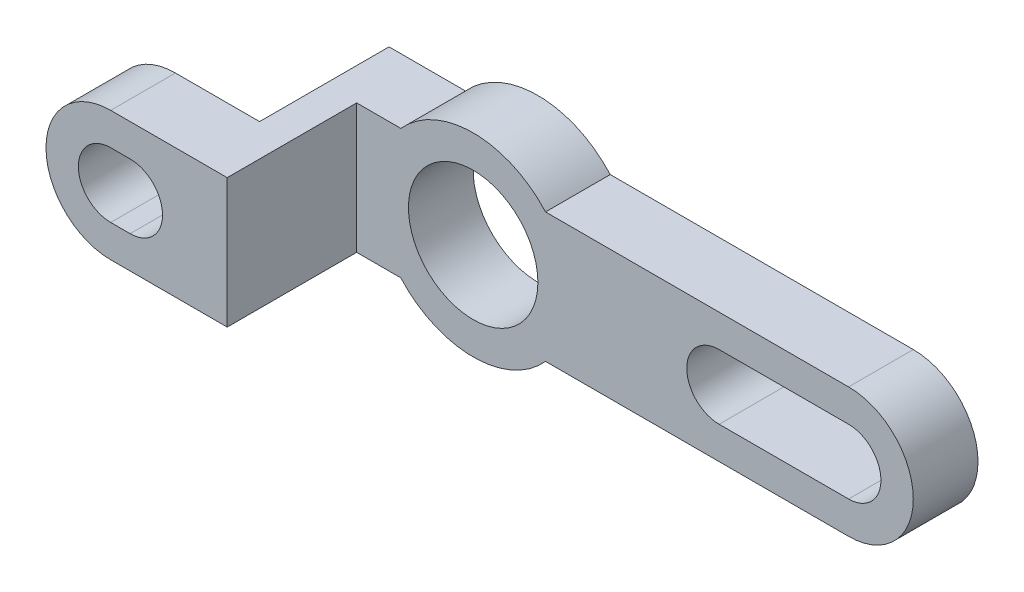
SolidWorks part; units mm, degrees
ref_plane "Front Plane" through (0, 0, 0) normal (0, 0, 1) x (1, 0, 0)
ref_plane "Top Plane" through (0, 0, 0) normal (0, 1, 0) x (1, 0, 0)
ref_plane "Right Plane" through (0, 0, 0) normal (1, 0, 0) x (0, 0, -1)
sketch "Sketch1" plane through (0, 0, 0) normal (0, 0, 1) x (1, 0, 0)
  line L0 (7.0995, 6.35) -> (31.75, 6.35)
  line L1 (-31.75, 6.35) -> (-7.0995, 6.35) construction
  line L2 (-31.75, 6.35) -> (-31.75, -6.35) construction
  line L3 (-31.75, -6.35) -> (-7.0995, -6.35) construction
  line L4 (31.75, 6.35) -> (31.75, -6.35) construction
  line L5 (-31.75, 6.35) -> (31.75, -6.35) construction
  line L6 (-31.75, -6.35) -> (31.75, 6.35) construction
  line L10 (7.0995, -6.35) -> (31.75, -6.35)
  line L14 (-17.78, 6.35) -> (-17.78, -6.35)
  line L15 (-17.78, 6.35) -> (-7.0995, 6.35)
  line L16 (-17.78, -6.35) -> (-7.0995, -6.35)
  line L17 (36.83, 6.35) -> (36.83, -6.35)
  line L18 (31.75, 6.35) -> (36.83, 6.35)
  line L19 (36.83, -6.35) -> (31.75, -6.35)
  arc A1 (-7.0995, -6.35) -> (7.0995, -6.35) centre (0, 0) ccw
  arc A5 (7.0995, 6.35) -> (-7.0995, 6.35) centre (0, 0) ccw
  circle A6 centre (0, 0) radius 6.35
  dimension "D3" = 19.05
  dimension "D4" = 12.7
  dimension "D1" = 63.5
  dimension "D2" = 12.7
  dimension "D5" = 13.97
  dimension "D6" = 36.83
extrude "Boss-Extrude1" add sketch "Sketch1" along normal mid plane 6.35
sketch "Sketch2" plane through (0, 0, -3.175) normal (0, 0, -1) x (-1, 0, 0)
  line L1 (-36.83, -6.35) -> (-36.83, 6.35) construction
  circle A0 centre (-36.83, 0) radius 6.35
  circle A1 centre (-36.83, 0) radius 3.175
  point P5 (-36.83, 0)
  dimension "D1" = 6.35
  dimension "D2" = 3.175
extrude "Boss-Extrude2" add sketch "Sketch2" against normal up to surface (6.35 mm away) up to face at (4.7625, 0, 3.175)
sketch "Sketch4" plane through (0, 0, 3.175) normal (0, 0, 1) x (1, 0, 0)
  line L1 (36.83, 3.175) -> (24.13, 3.175)
  line L2 (36.83, -3.175) -> (24.13, -3.175)
  arc A1 (36.83, -3.175) -> (36.83, 3.175) centre (36.83, 0) ccw construction
  arc A2 (36.83, -3.175) -> (36.83, 3.175) centre (36.83, 0) ccw construction
  arc A3 (36.83, -3.175) -> (36.83, 3.175) centre (36.83, 0) ccw
  arc A4 (24.13, 3.175) -> (24.13, -3.175) centre (24.13, 0) ccw
  arc A5 (24.13, -3.175) -> (24.13, 3.175) centre (24.13, 0) ccw construction
  arc A6 (36.83, 3.175) -> (36.83, -3.175) centre (36.83, 0) ccw construction
  point P8 (0, 0)
  point P9 (18.0445, 0)
  point P10 (19.3259, 0)
  point P11 (19.5015, 0)
  dimension "D1" = 12.7
extrude "Cut-Extrude2" cut sketch "Sketch4" against normal up to surface (6.35 mm away) up to face at (5.5562, 0, -3.175)
sketch "Sketch5" plane through (0, 0, 3.175) normal (0, 0, 1) x (1, 0, 0)
  line L1 (-17.78, 6.35) -> (-11.43, 6.35)
  line L2 (-17.78, 6.35) -> (-17.78, -6.35)
  line L3 (-17.78, -6.35) -> (-11.43, -6.35)
  line L4 (-11.43, 6.35) -> (-11.43, -6.35)
  dimension "D1" = 6.35
extrude "Boss-Extrude3" add sketch "Sketch5" along normal blind 12.7
sketch "Sketch6" plane through (-17.78, 0, 0) normal (-1, 0, 0) x (0, 0, 1)
  line L0 (15.875, -6.35) -> (-3.175, -6.35) construction
  line L1 (15.875, 6.35) -> (9.525, 6.35)
  line L2 (15.875, 6.35) -> (15.875, -6.35)
  line L3 (15.875, -6.35) -> (9.525, -6.35)
  line L4 (9.525, 6.35) -> (9.525, -6.35)
  dimension "D1" = 6.35
extrude "Boss-Extrude4" add sketch "Sketch6" along normal blind 5.08
sketch "Sketch7" plane through (0, 0, 15.875) normal (0, 0, 1) x (1, 0, 0)
  line L0 (-22.86, -6.35) -> (-22.86, 6.35) construction
  line L2 (-22.86, -6.35) -> (-11.43, -6.35) construction
  circle A0 centre (-22.86, 0) radius 3.175
  circle A1 centre (-22.86, 0) radius 6.35
  dimension "D1" = 6.35
extrude "Boss-Extrude5" add sketch "Sketch7" against normal up to surface (6.35 mm away) up to face at (-20.32, 0, 9.525)
sketch "Sketch8" plane through (0, 0, 15.875) normal (0, 0, 1) x (1, 0, 0)
  line L0 (-17.78, 6.35) -> (-17.78, -6.35) construction
  line L1 (-17.78, 6.35) -> (-17.78, -6.35) construction
  line L2 (-22.86, 3.175) -> (-20.955, 3.175)
  line L3 (-20.955, -3.175) -> (-22.86, -3.175)
  arc A1 (-22.86, 3.175) -> (-22.86, -3.175) centre (-22.86, 0) ccw construction
  arc A2 (-22.86, 3.175) -> (-22.86, -3.175) centre (-22.86, 0) ccw
  arc A3 (-20.955, -3.175) -> (-20.955, 3.175) centre (-20.955, 0) ccw
extrude "Cut-Extrude3" cut sketch "Sketch8" against normal up to surface (6.35 mm away) up to face at (-21.9075, 0, 9.525)
ref_plane "Midplane for Mates" through (0, 0, 12.7) normal (0, 0, 1) x (1, 0, 0)
sketch "Sketch9" plane through (-17.78, 0, 0) normal (-1, 0, 0) x (0, 0, 1)
  line L5 (9.525, 0) -> (9.525, 6.35)
  line L6 (9.525, 6.35) -> (-3.175, 6.35)
  line L7 (-3.175, 6.35) -> (-3.175, -6.35)
  line L8 (-3.175, -6.35) -> (9.525, -6.35)
  line L9 (9.525, -6.35) -> (9.525, 0)
  line L10 (9.525, 0) -> (9.525, 6.35)
  line L11 (9.525, 6.35) -> (-3.175, 6.35)
  line L12 (-3.175, 6.35) -> (-3.175, -6.35)
  line L13 (-3.175, -6.35) -> (9.525, -6.35)
  line L14 (9.525, -6.35) -> (9.525, 0)
  dimension "D1" = 0
extrude "Cut-Extrude4" cut sketch "Sketch9" against normal offset from surface (3.175 mm away) 3.175 up to face at (-11.43, 0, 9.525)
